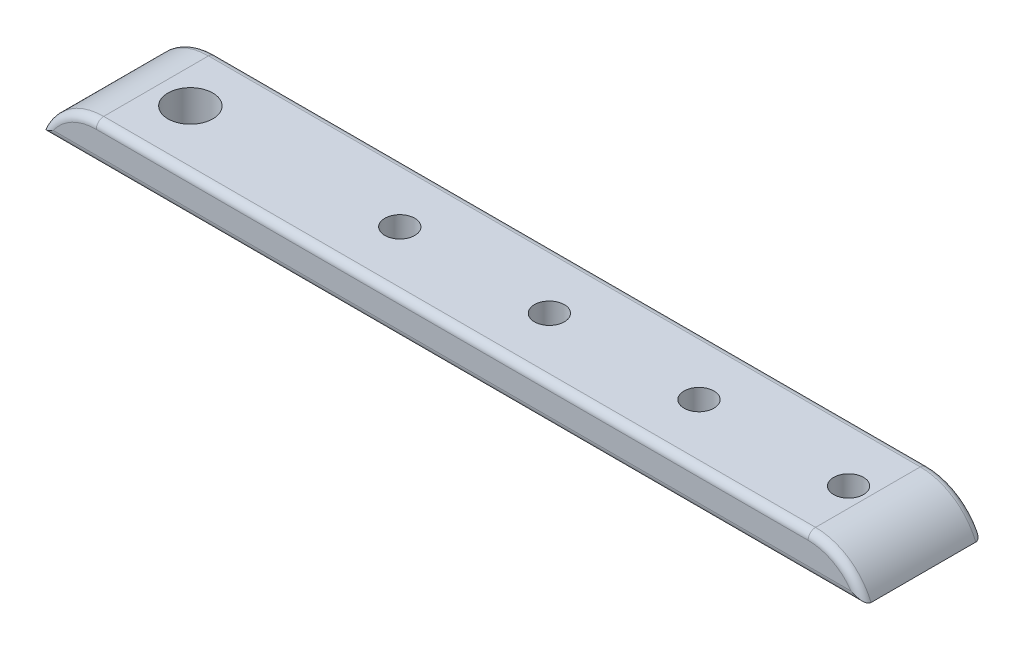
SolidWorks part; units mm, degrees
material "ABS"
ref_plane "Front Plane" through (0, 0, 0) normal (0, 0, 1) x (1, 0, 0)
ref_plane "Top Plane" through (0, 0, 0) normal (0, 1, 0) x (1, 0, 0)
ref_plane "Right Plane" through (0, 0, 0) normal (1, 0, 0) x (0, 0, -1)
sketch "Sketch2" plane through (0, 0, 0) normal (0, 1, 0) x (1, 0, 0)
  line L1 (-55, 8) -> (55, 8)
  line L2 (-55, 8) -> (-55, -8)
  line L3 (-55, -8) -> (55, -8)
  line L4 (55, 8) -> (55, -8)
  line L5 (-55, 8) -> (55, -8) construction
  line L6 (-55, -8) -> (55, 8) construction
  point P0 (0, 0)
  dimension "D1" = 110
  dimension "D2" = 16
extrude "Boss-Extrude1" add sketch "Sketch2" along normal blind 5
sketch "Sketch3" plane through (0, 5, 0) normal (0, 1, 0) x (1, 0, 0)
  line L0 (-55, 8) -> (-55, -8) construction
  line L1 (55, 8) -> (-55, 8) construction
  circle A0 centre (-43, 0) radius 3
  dimension "D1" = 6
  dimension "D2" = 12
  dimension "D3" = 8
extrude "Cut-Extrude1" cut sketch "Sketch3" against normal through all
sketch "Sketch5" plane through (0, 5, 0) normal (0, 1, 0) x (1, 0, 0)
  circle A0 centre (-15, 0) radius 2
  circle A1 centre (5, 0) radius 2
  circle A2 centre (25, 0) radius 2
  circle A3 centre (45, 0) radius 2
  dimension "D1" = 4
  dimension "D2" = 4
  dimension "D3" = 4
  dimension "D4" = 4
  dimension "D5" = 15
  dimension "D6" = 5
  dimension "D7" = 25
  dimension "D8" = 45
extrude "Cut-Extrude2" cut sketch "Sketch5" against normal through all
fillet "Fillet1" radius 8 2 edges at (55, 5, 0) (-55, 5, 0)
fillet "Fillet2" radius 1 8 edges at (-52.0559, 3.6332, 8) (52.0559, 3.6332, 8) (52.0559, 3.6332, -8) (-52.0559, 3.6332, -8) (0, 0, 8) (0, 5, 8) (0, 0, -8) (0, 5, -8)
